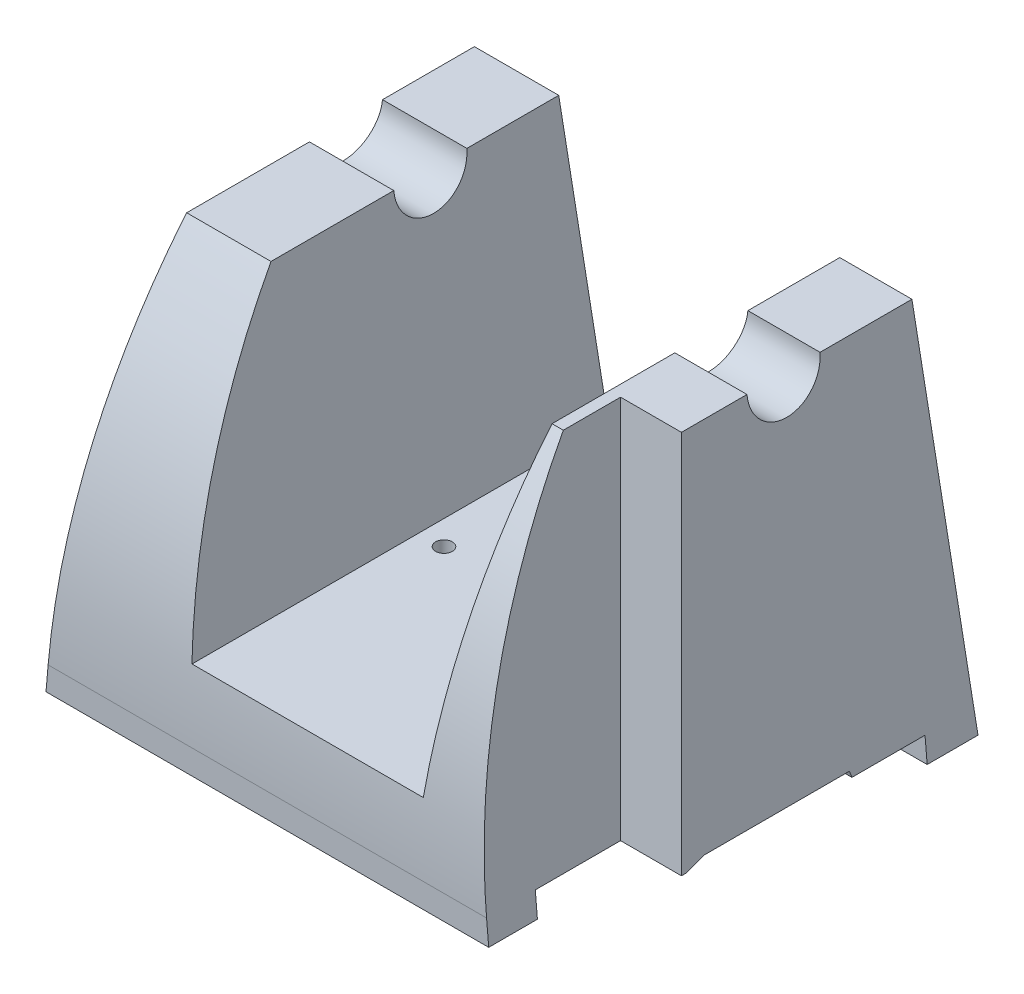
SolidWorks part; units mm, degrees
material "6061 Alloy"
ref_plane "Front Plane" through (0, 0, 0) normal (0, 0, 1) x (1, 0, 0)
ref_plane "Top Plane" through (0, 0, 0) normal (0, 1, 0) x (1, 0, 0)
ref_plane "Right Plane" through (0, 0, 0) normal (1, 0, 0) x (0, 0, -1)
sketch "Sketch1" plane through (0, 0, 0) normal (1, 0, 0) x (0, 0, -1)
  line L0 (0, 0) -> (0, 6.35)
  line L1 (28.0591, 98.425) -> (60.0671, 98.425)
  line L2 (111.125, 98.425) -> (111.125, 0)
  line L3 (111.125, 0) -> (98.425, 0)
  line L4 (98.425, 0) -> (98.425, 6.35)
  line L5 (98.425, 6.35) -> (79.375, 6.35)
  line L6 (79.375, 6.35) -> (78.8395, 7.9375)
  line L7 (78.8395, 7.9375) -> (40.8808, 7.9375)
  line L8 (40.8808, 7.9375) -> (36.1749, 6.35)
  line L9 (36.1749, 6.35) -> (12.7, 6.35)
  line L10 (12.7, 6.35) -> (12.7, 0)
  line L11 (12.7, 0) -> (0, 0)
  line L12 (28.0591, 98.425) -> (28.0591, 70.551) construction
  line L13 (79.1171, 98.425) -> (111.125, 98.425)
  line L14 (28.0591, 98.425) -> (111.125, 98.425) construction
  arc A0 (0, 6.35) -> (28.0591, 98.425) centre (165.1, 6.35) cw
  arc A1 (60.0671, 98.425) -> (79.1171, 98.425) centre (69.5921, 98.425) ccw
  dimension "D8" = 165.1
  dimension "D10" = 19.05
  dimension "D1" = 6.35
  dimension "D2" = 1.5875
  dimension "D3" = 12.7
  dimension "D4" = 12.7
  dimension "D5" = 6.35
  dimension "D6" = 19.05
  dimension "D7" = 98.425
  dimension "D9" = 111.125
extrude "Boss-Extrude1" add sketch "Sketch1" along normal blind 130.175
sketch "Sketch2" plane through (0, 0, -111.125) normal (0, 0, -1) x (-1, 0, 0)
  line L0 (-95.25, 98.425) -> (-95.25, 24.3211)
  line L1 (-130.175, 98.425) -> (0, 98.425) construction
  line L2 (-95.25, 24.3211) -> (-38.1, 24.3211)
  line L3 (-38.1, 24.3211) -> (-38.1, 98.425)
  line L4 (-130.175, 0) -> (-130.175, 98.425) construction
  line L5 (0, 0) -> (0, 98.425) construction
  line M4 (0, 98.425) -> (-130.175, 98.425)
  dimension "D1" = 34.925
  dimension "D2" = 38.1
extrude "Cut-Extrude1" cut sketch "Sketch2" against normal through all and the other way through all contours L2 L3 L0 M4 region at (66.675, 61.373, -111.125)
sketch "Sketch3" plane through (0, 98.425, 0) normal (0, 1, 0) x (1, 0, 0)
  line L0 (130.175, 111.125) -> (95.25, 111.125) construction
  line L1 (130.175, 0) -> (114.3, 0)
  line L2 (130.175, 0) -> (130.175, 34.925)
  line L3 (130.175, 34.925) -> (114.3, 34.925)
  line L4 (114.3, 0) -> (114.3, 34.925)
  dimension "D1" = 15.875
  dimension "D2" = 76.2
extrude "Cut-Extrude2" cut sketch "Sketch3" against normal through all
draft "Draft1" type of draft neutral plane draft angle 5 faces to draft 7 face at (65.8812, 55.2928, -111.125) face at (122.2375, 52.3875, -34.925) face at (130.175, 35.4542, -71.9504) face at (114.3, 31.1415, -16.6357) face at (95.25, 72.4097, -64.3304) face at (0, 28.926, -56.0103) face at (38.1, 72.4097, -64.3304) neutral plane through (130.175, 6.35, -36.1749) neutral plane normal (0, -1, 0) reverse direction yes parameters "D1"=5
sketch "Sketch4" plane through (0, 24.3211, 0) normal (0, 1, 0) x (1, 0, 0)
  circle A0 centre (42.8697, 60.325) radius 2.1784
extrude "Cut-Extrude3" cut sketch "Sketch4" against normal through all both and the other way through all
